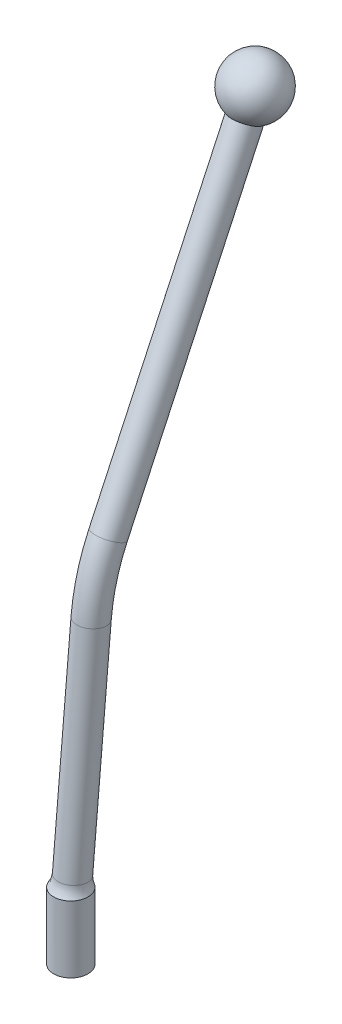
SolidWorks part; units mm, degrees
ref_plane "前视基准面" through (0, 0, 0) normal (0, 0, 1) x (1, 0, 0)
ref_plane "上视基准面" through (0, 0, 0) normal (0, 1, 0) x (1, 0, 0)
ref_plane "右视基准面" through (0, 0, 0) normal (1, 0, 0) x (0, 0, -1)
other "Configuration Table"
sketch "草图1" plane through (0, 0, 0) normal (0, 1, 0) x (1, 0, 0)
  circle A0 centre (0, 0) radius 0.9
  dimension "D1" = 1.8
extrude "凸台-拉伸1" add sketch "草图1" along normal blind 3.5
sketch "草图2" plane through (0, 0, 0) normal (1, 0, 0) x (0, 0, -1)
  line L0 (9.6725, 35.0729) -> (1.9654, 18.5448)
  line L1 (1.0665, 15.1902) -> (0, 3)
  line L3 (0.9, 3.5) -> (-0.9, 3.5) construction
  arc A0 (1.0665, 15.1902) -> (1.9654, 18.5448) centre (11.0284, 14.3186) cw
  point P2 (1.0114, 8.6945)
  point P4 (0, 2.5327)
  point P5 (0, 2.6165)
  point P6 (1.3317, 14.9586)
  point P7 (4.9213, 18.2784)
  point P8 (4.6406, 21.0682)
  point P9 (1.7973, 17.7851)
  point P10 (5.1004, 27.8149)
  point P11 (7.1263, 28.7253)
  point P12 (2.3613, 15.9206)
  point P13 (9.0196, 28.1832)
  point P14 (0, 0)
  point P15 (0, 0)
  point P21 (1.2202, 16.9467)
  dimension "D6" = 10
  dimension "D1" = 0.5
  dimension "D2" = 160
  dimension "D3" = 14
  dimension "D4" = 20
  dimension "D5" = 85
ref_plane "基准面1" through (0, 3, 0) normal (0, -0.9962, 0.0872) x (-1, 0, 0)
sweep "扫描1" add path "草图2" circular profile diameter 1.5 parameters "D3"=1.5
sketch "草图20" plane through (0, 32.5134, -15.1613) normal (0, 0.9063, -0.4226) x (1, 0, 0)
  line L0 (0, -6.0561) -> (-1.5, -6.0561) construction
  circle A0 centre (0, -6.0561) radius 1.5
  circle A1 centre (0, -6.0561) radius 0.75 construction
  dimension "D1" = 3
revolve "旋转7" add sketch "草图20" angle 360 about L0 region at (0, 34.4569, -10.9936)
fillet "圆角2" radius 1 1 edges at (0, 3.5, 0.7091)
